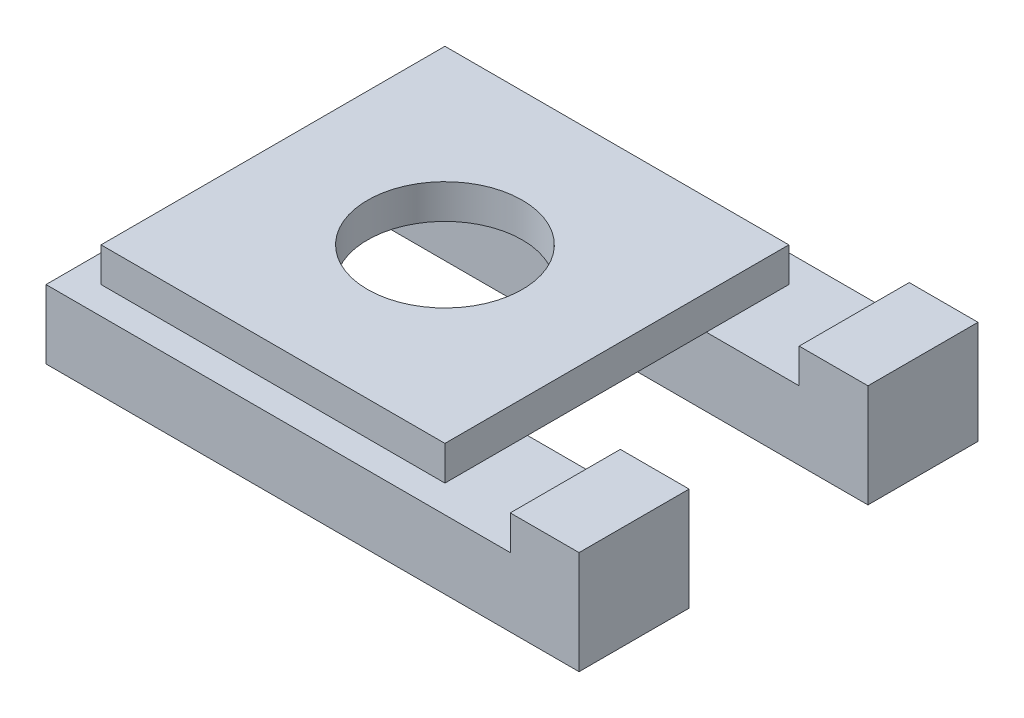
SolidWorks part; units mm, degrees
ref_plane "Front Plane" through (0, 0, 0) normal (0, 0, 1) x (1, 0, 0)
ref_plane "Top Plane" through (0, 0, 0) normal (0, 1, 0) x (1, 0, 0)
ref_plane "Right Plane" through (0, 0, 0) normal (1, 0, 0) x (0, 0, -1)
sketch "Sketch1" plane through (0, 0, 0) normal (0, 1, 0) x (1, 0, 0)
  line L0 (-55, 0) -> (55, 0) construction
  line L1 (-50, -50) -> (50, -50)
  line L2 (-50, -50) -> (-50, 50)
  line L3 (-50, 50) -> (50, 50)
  line L4 (50, -50) -> (50, 50)
  line L5 (-50, -50) -> (50, 50) construction
  line L6 (-50, 50) -> (50, -50) construction
  line L7 (-58, 58) -> (77, 58)
  line L8 (-58, 58) -> (-58, 26)
  line L9 (-58, 26) -> (-50, 26)
  line L10 (77, 58) -> (77, 26)
  line L11 (77, 26) -> (97, 26)
  line L12 (77, 26) -> (77, 58)
  line L13 (77, 58) -> (97, 58)
  line L14 (97, 26) -> (97, 58)
  line L15 (97, -26) -> (97, -58)
  line L16 (77, -58) -> (97, -58)
  line L17 (77, -26) -> (77, -58)
  line L18 (77, -26) -> (97, -26)
  line L19 (77, -58) -> (77, -26)
  line L20 (-58, -26) -> (-50, -26)
  line L21 (-58, -58) -> (-58, -26)
  line L22 (-58, -58) -> (77, -58)
  line L23 (-50, -50) -> (50, -50)
  line L24 (50, -26) -> (77, -26)
  line L25 (50, 26) -> (77, 26)
  line L26 (50, -26) -> (-50, -26)
  line L27 (-50, 26) -> (50, 26)
  circle A0 centre (0, 0) radius 22.5
  dimension "D3" = 45
  dimension "D1" = 100
  dimension "D2" = 100
  dimension "D4" = 8
  dimension "D5" = 32
  dimension "D6" = 20
  dimension "D7" = 8
  dimension "D8" = 155
extrude "Boss-Extrude1" add sketch "Sketch1" along normal blind 20 contours L24 L4 L1 L2 L20 L21 L22 L17 | L4 L25 L10 L7 L8 L9 L2 L3 | L18 L17 L16 L15 | L11 L14 L13 L10 | L4 L26 L2 L1 | L2 L27 L4 L3 region at (0, 0, 38) region at (0, 0, 51.3874) region at (-54, 0, -27.3874) region at (0, 0, -38) region at (87, 0, 42) region at (87, 0, -42)
extrude "Boss-Extrude2" add sketch "Sketch1<3>" along normal blind 10 from surface contours L18 L17 L16 L15 | L11 L14 L13 L10 region at (87, 0, 42) region at (87, 0, -42) starting at face at (19.5, 20, 42)
sketch "Sketch1<3>" plane through (0, 0, 0) normal (0, 1, 0) x (1, 0, 0) same geometry as "Sketch1"
extrude "Boss-Extrude3" add sketch "Sketch1<5>" along normal blind 10 from surface contours L4 L26 L2 L1 | L27 L2 L26 L4 A0 | L2 L27 L4 L3 region at (0, 0, 38) region at (-48.8729, 0, 0) region at (0, 0, -38) starting at face at (9.5, 20, 42)
sketch "Sketch1<5>" plane through (0, 0, 0) normal (0, 1, 0) x (1, 0, 0) same geometry as "Sketch1"
